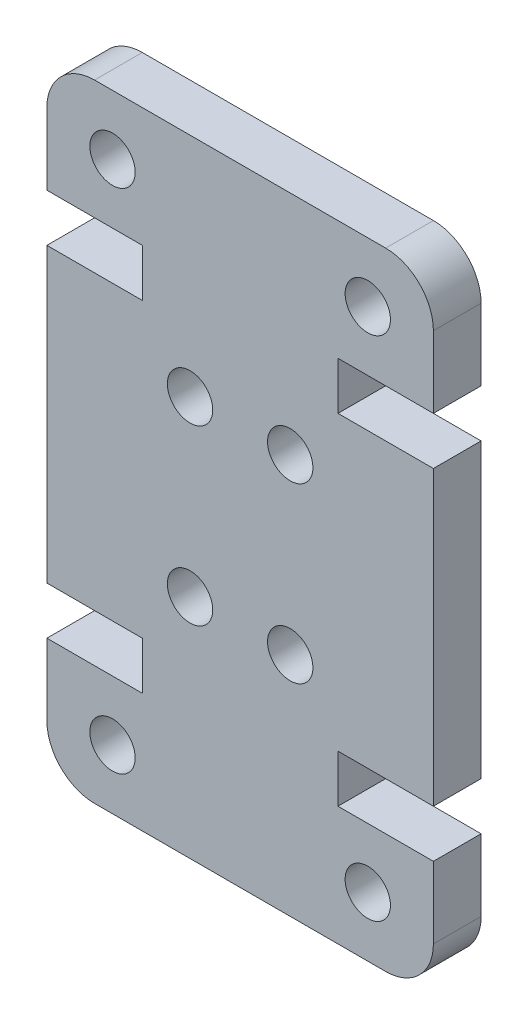
SolidWorks part; units mm, degrees
ref_plane "Front Plane" through (0, 0, 0) normal (0, 0, 1) x (1, 0, 0)
ref_plane "Top Plane" through (0, 0, 0) normal (0, 1, 0) x (1, 0, 0)
ref_plane "Right Plane" through (0, 0, 0) normal (1, 0, 0) x (0, 0, -1)
sketch "Sketch2" plane through (0, 0, 0) normal (0, 0, 1) x (1, 0, 0)
  line L0 (0, 13.13) -> (16.2, 13.13) construction
  line L1 (8.1, 26.26) -> (8.1, 0) construction
  line L2 (0, 7) -> (0, 19.26)
  line L3 (2, 0) -> (14.2, 0)
  line L4 (16.2, 2) -> (16.2, 5)
  line L5 (12.2, 5) -> (16.2, 5)
  line L6 (16.2, 7) -> (12.2, 7)
  line L7 (12.2, 7) -> (12.2, 5)
  line L8 (16.2, 7) -> (16.2, 19.26)
  line L9 (0, 24.26) -> (0, 21.26)
  line L10 (4, 21.26) -> (0, 21.26)
  line L11 (0, 19.26) -> (4, 19.26)
  line L12 (4, 19.26) -> (4, 21.26)
  line L13 (12.2, 19.26) -> (12.2, 21.26)
  line L14 (16.2, 19.26) -> (12.2, 19.26)
  line L15 (12.2, 21.26) -> (16.2, 21.26)
  line L16 (16.2, 24.26) -> (16.2, 21.26)
  line L17 (2, 26.26) -> (14.2, 26.26)
  line L27 (4, 7) -> (4, 5)
  line L30 (0, 7) -> (4, 7)
  line L32 (4, 5) -> (0, 5)
  line L36 (0, 2) -> (0, 5)
  circle A0 centre (13.45, 2.5) radius 0.95
  circle A1 centre (10.2, 9.5) radius 0.95
  arc A2 (16.2, 2) -> (14.2, 0) centre (14.2, 2) cw
  circle A3 centre (2.75, 23.76) radius 0.95
  circle A4 centre (6, 16.76) radius 0.95
  arc A5 (0, 24.26) -> (2, 26.26) centre (2, 24.26) cw
  arc A6 (16.2, 24.26) -> (14.2, 26.26) centre (14.2, 24.26) ccw
  circle A7 centre (10.2, 16.76) radius 0.95
  circle A8 centre (13.45, 23.76) radius 0.95
  arc A17 (0, 2) -> (2, 0) centre (2, 2) ccw
  circle A19 centre (6, 9.5) radius 0.95
  circle A21 centre (2.75, 2.5) radius 0.95
  point P16 (8.1, 13.13)
  dimension "D1" = 1.9
  dimension "D2" = 2
  dimension "D3" = 2.75
  dimension "D4" = 6
  dimension "D5" = 8.1
  dimension "D6" = 2.5
  dimension "D9" = 9.5
  dimension "D10" = 13.13
  dimension "D7" = 5
extrude "Boss-Extrude1" add sketch "Sketch2" along normal blind 4
sketch "Sketch3" plane through (0, 0, 4) normal (0, 0, 1) x (1, 0, 0)
  line L0 (0, 0) -> (0, 26.26)
  line L1 (0, 26.26) -> (16.2, 26.26)
  line L2 (16.2, 26.26) -> (16.2, 0)
  line L3 (16.2, 0) -> (0, 0)
extrude "Cut-Extrude1" cut sketch "Sketch3" against normal blind 2
equation "\"D5@Sketch2\"= \"fingerWidth@parametersSketch@prostheticParameters.SLDPRT\" / 2'Finger Width"
equation "\"D10@Sketch2\"= ( ( \"HL@parametersSketch@prostheticParameters.SLDPRT\" * 0.196 ) - 4 - 6 ) / 2 'PIP Length"
equation "\"D1@Sketch2\"= 1.5 + \"tol1@parametersSketch@prostheticParameters.SLDPRT\""
